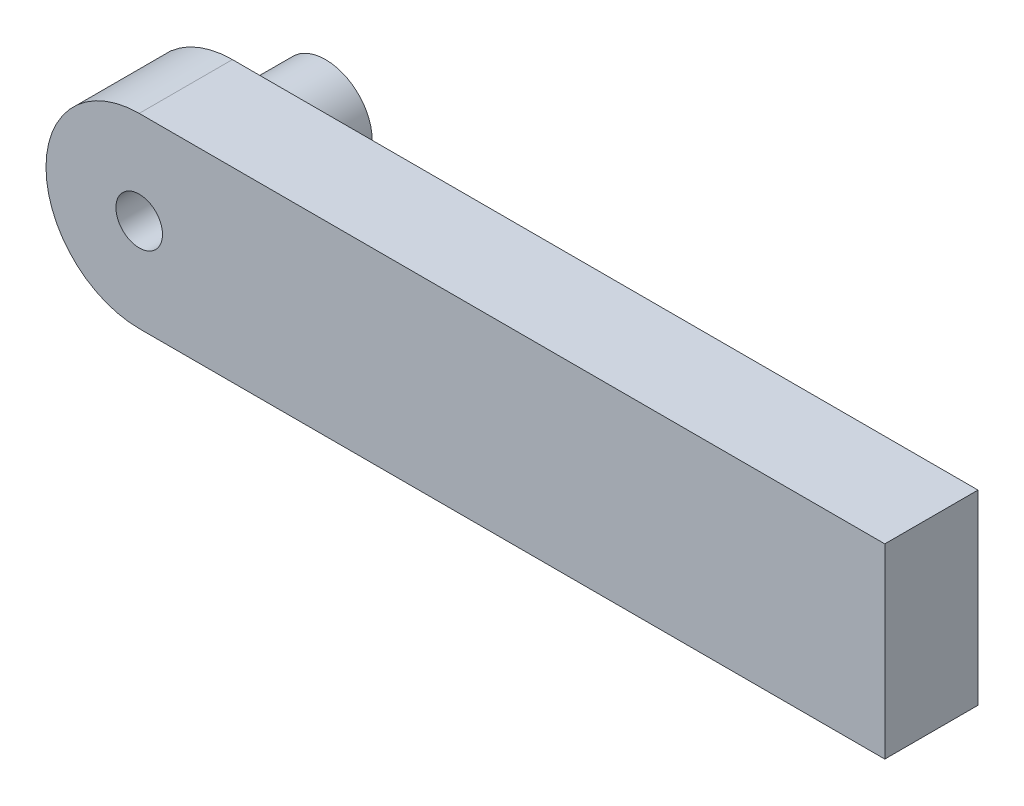
SolidWorks part; units mm, degrees
material "PET"
ref_plane "Piano frontale" through (0, 0, 0) normal (0, 0, 1) x (1, 0, 0)
ref_plane "Piano superiore" through (0, 0, 0) normal (0, 1, 0) x (1, 0, 0)
ref_plane "Piano destro" through (0, 0, 0) normal (1, 0, 0) x (0, 0, -1)
sketch "Schizzo1" plane through (0, 0, 0) normal (0, 0, 1) x (1, 0, 0)
  line L0 (20, 4.5035) -> (-20, 4.5035)
  line L2 (-20, -5.4965) -> (20, -5.4965)
  line L12 (20, 4.5035) -> (20, -5.4965)
  arc A0 (-20, 4.5035) -> (-20, -5.4965) centre (-20, -0.4965) ccw
  dimension "D1" = 10
  dimension "D9" = 40
extrude "Estrusione-Estrusione1" add sketch "Schizzo1" along normal blind 5
sketch "Schizzo2" plane through (0, 0, 0) normal (0, 0, -1) x (-1, 0, 0)
  arc A0 (20, -5.4965) -> (20, 4.5035) centre (20, -0.4965) ccw construction
  arc A1 (20, -5.4965) -> (20, 4.5035) centre (20, -0.4965) ccw construction
  circle A2 centre (20, -0.4965) radius 2.5
extrude "Estrusione-Estrusione2" add sketch "Schizzo2" along normal blind 5 contours A2
sketch "Schizzo3" plane through (0, 0, -5) normal (0, 0, -1) x (-1, 0, 0)
  circle A0 centre (20, -0.4965) radius 1.25
  dimension "D1" = 2.5
extrude "Taglio-Estrusione1" cut sketch "Schizzo3" against normal through all
ref_point "Punto1"
ref_axis "Assi1" through (-20, -0.4965, 5) along (0, 0, -1)
ref_axis "Assi2" through (20, 4.5035, 0) along (-1, 0, 0)
sketch "Schizzo4" plane through (0, 0, 0) normal (0, 0, -1) x (-1, 0, 0)
  line L0 (20, -0.4965) -> (2.37, -0.4965)
  dimension "D1" = 17.63
ref_plane "Piano1" through (-2.37, 0, 0) normal (1, 0, 0) x (0, 0, -1)
sketch "Schizzo5" plane through (-2.37, 0, 0) normal (1, 0, 0) x (0, 0, -1)
  line L0 (0, -0.4965) -> (-2.34, -0.4965)
  dimension "D1" = 2.34
